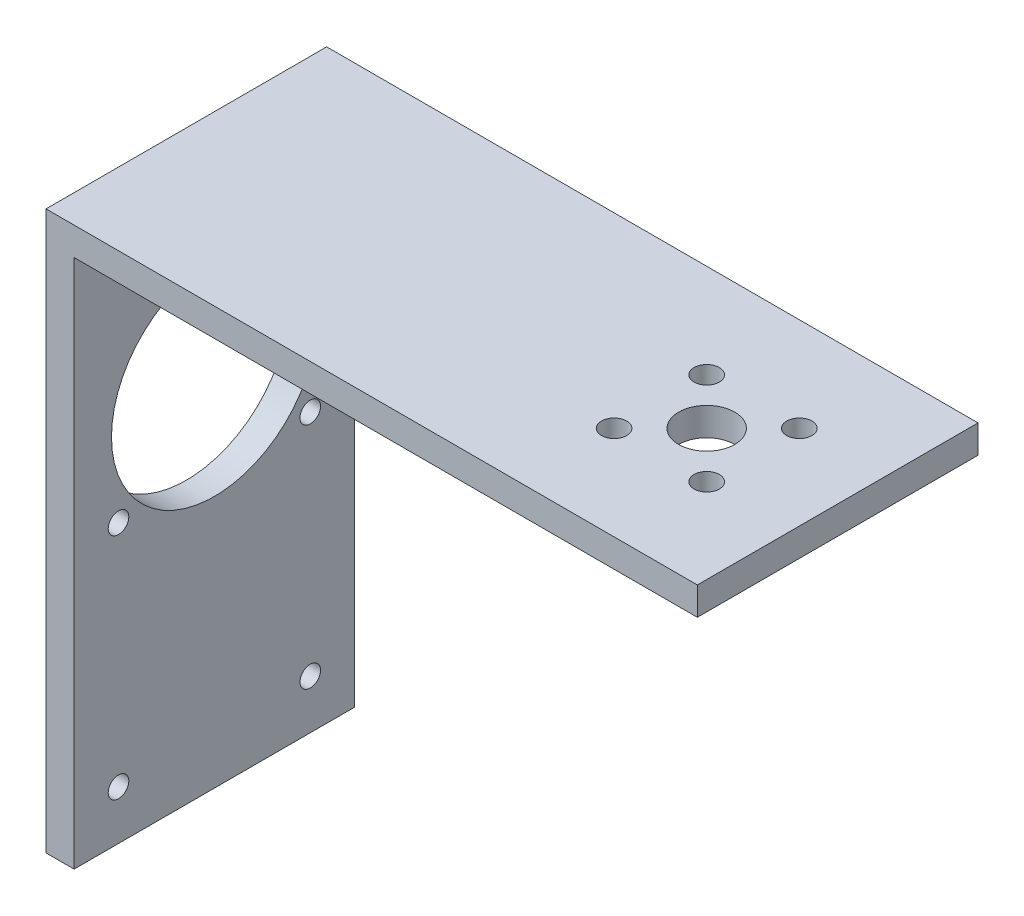
SolidWorks part; units mm, degrees
ref_plane "Front Plane" through (0, 0, 0) normal (0, 0, 1) x (1, 0, 0)
ref_plane "Top Plane" through (0, 0, 0) normal (0, 1, 0) x (1, 0, 0)
ref_plane "Right Plane" through (0, 0, 0) normal (1, 0, 0) x (0, 0, -1)
ref_plane "PZ_m15_000" through (0, 0, -15) normal (0, 0, 1) x (1, 0, 0)
sketch "S_box1" plane through (0, 0, -15) normal (0, 0, 1) x (1, 0, 0)
  line L0 (-55.625, 18.625) -> (14, 18.625)
  line L1 (14, 18.625) -> (14, 21.625)
  line L2 (14, 21.625) -> (-55.625, 21.625)
  line L3 (-55.625, 21.625) -> (-55.625, 18.625)
  dimension "P1" = 55.625
  dimension "P2" = 18.625
  dimension "P3" = 14
  dimension "P4" = 18.625
  dimension "P5" = 14
  dimension "P6" = 21.625
  dimension "P7" = 55.625
  dimension "P8" = 21.625
extrude "Boss_1" add sketch "S_box1" along normal blind 30
sketch "S_box2" plane through (0, 0, -15) normal (0, 0, 1) x (1, 0, 0)
  line L0 (-55.625, -38) -> (-52.625, -38)
  line L1 (-52.625, -38) -> (-52.625, 19.125)
  line L2 (-52.625, 19.125) -> (-55.625, 19.125)
  line L3 (-55.625, 19.125) -> (-55.625, -38)
  dimension "P1" = 55.625
  dimension "P2" = 38
  dimension "P3" = 52.625
  dimension "P4" = 38
  dimension "P5" = 52.625
  dimension "P6" = 19.125
  dimension "P7" = 55.625
  dimension "P8" = 19.125
extrude "Boss_2" add sketch "S_box2" along normal blind 30
sketch "S_box3" plane through (0, 0, -15) normal (0, 0, 1) x (1, 0, 0)
  line L0 (-53.125, 15.625) -> (-24, 15.625)
  line L1 (-24, 15.625) -> (-24, 19.125)
  line L2 (-24, 19.125) -> (-53.125, 19.125)
  line L3 (-53.125, 19.125) -> (-53.125, 15.625)
  dimension "P1" = 53.125
  dimension "P2" = 15.625
  dimension "P3" = 24
  dimension "P4" = 15.625
  dimension "P5" = 24
  dimension "P6" = 19.125
  dimension "P7" = 53.125
  dimension "P8" = 19.125
extrude "Boss_3" add sketch "S_box3" along normal blind 3
ref_plane "PY_p18_525" through (0, 18.525, 0) normal (0, 1, 0) x (1, 0, 0)
sketch "S_hole4" plane through (0, 18.525, 0) normal (0, 1, 0) x (1, 0, 0)
  circle A0 centre (0, 0) radius 3
  dimension "D1_S_hole4" = 6
extrude "Hole_4" cut sketch "S_hole4" along normal blind 3.2
sketch "S_hole5" plane through (0, 18.525, 0) normal (0, 1, 0) x (1, 0, 0)
  circle A0 centre (4.9497, -4.9497) radius 1.35
  dimension "D1_S_hole5" = 2.7
  dimension "P2" = 4.9497
  dimension "P3" = 4.9497
extrude "Hole_5" cut sketch "S_hole5" along normal blind 3.2
sketch "S_hole6" plane through (0, 18.525, 0) normal (0, 1, 0) x (1, 0, 0)
  circle A0 centre (-4.9497, -4.9497) radius 1.35
  dimension "D1_S_hole6" = 2.7
  dimension "P2" = 4.9497
  dimension "P3" = 4.9497
extrude "Hole_6" cut sketch "S_hole6" along normal blind 3.2
sketch "S_hole7" plane through (0, 18.525, 0) normal (0, 1, 0) x (1, 0, 0)
  circle A0 centre (-4.9497, 4.9497) radius 1.35
  dimension "D1_S_hole7" = 2.7
  dimension "P2" = 4.9497
  dimension "P3" = 4.9497
extrude "Hole_7" cut sketch "S_hole7" along normal blind 3.2
sketch "S_hole8" plane through (0, 18.525, 0) normal (0, 1, 0) x (1, 0, 0)
  circle A0 centre (4.9497, 4.9497) radius 1.35
  dimension "D1_S_hole8" = 2.7
  dimension "P2" = 4.9497
  dimension "P3" = 4.9497
extrude "Hole_8" cut sketch "S_hole8" along normal blind 3.2
ref_plane "PX_m55_725" through (-55.725, 0, 0) normal (1, 0, 0) x (0, 0, -1)
sketch "S_hole9" plane through (-55.725, 0, 0) normal (1, 0, 0) x (0, 0, -1)
  circle A0 centre (0, 0) radius 11
  dimension "D1_S_hole9" = 22
extrude "Hole_9" cut sketch "S_hole9" along normal blind 3.2
sketch "S_hole10" plane through (-55.725, 0, 0) normal (1, 0, 0) x (0, 0, -1)
  circle A0 centre (10.25, -8.3) radius 1.1
  dimension "D1_S_hole10" = 2.2
  dimension "P2" = 10.25
  dimension "P3" = 8.3
extrude "Hole_10" cut sketch "S_hole10" along normal blind 3.2
sketch "S_hole11" plane through (-55.725, 0, 0) normal (1, 0, 0) x (0, 0, -1)
  circle A0 centre (-10.25, -8.3) radius 1.1
  dimension "D1_S_hole11" = 2.2
  dimension "P2" = 10.25
  dimension "P3" = 8.3
extrude "Hole_11" cut sketch "S_hole11" along normal blind 3.2
sketch "S_hole12" plane through (-55.725, 0, 0) normal (1, 0, 0) x (0, 0, -1)
  circle A0 centre (10.25, -32.75) radius 1.1
  dimension "D1_S_hole12" = 2.2
  dimension "P2" = 10.25
  dimension "P3" = 32.75
extrude "Hole_12" cut sketch "S_hole12" along normal blind 3.2
sketch "S_hole13" plane through (-55.725, 0, 0) normal (1, 0, 0) x (0, 0, -1)
  circle A0 centre (-10.25, -32.75) radius 1.1
  dimension "D1_S_hole13" = 2.2
  dimension "P2" = 10.25
  dimension "P3" = 32.75
extrude "Hole_13" cut sketch "S_hole13" along normal blind 3.2
equation "\"plate_t\" = 3"
equation "\"clearance\" = 0.4"
